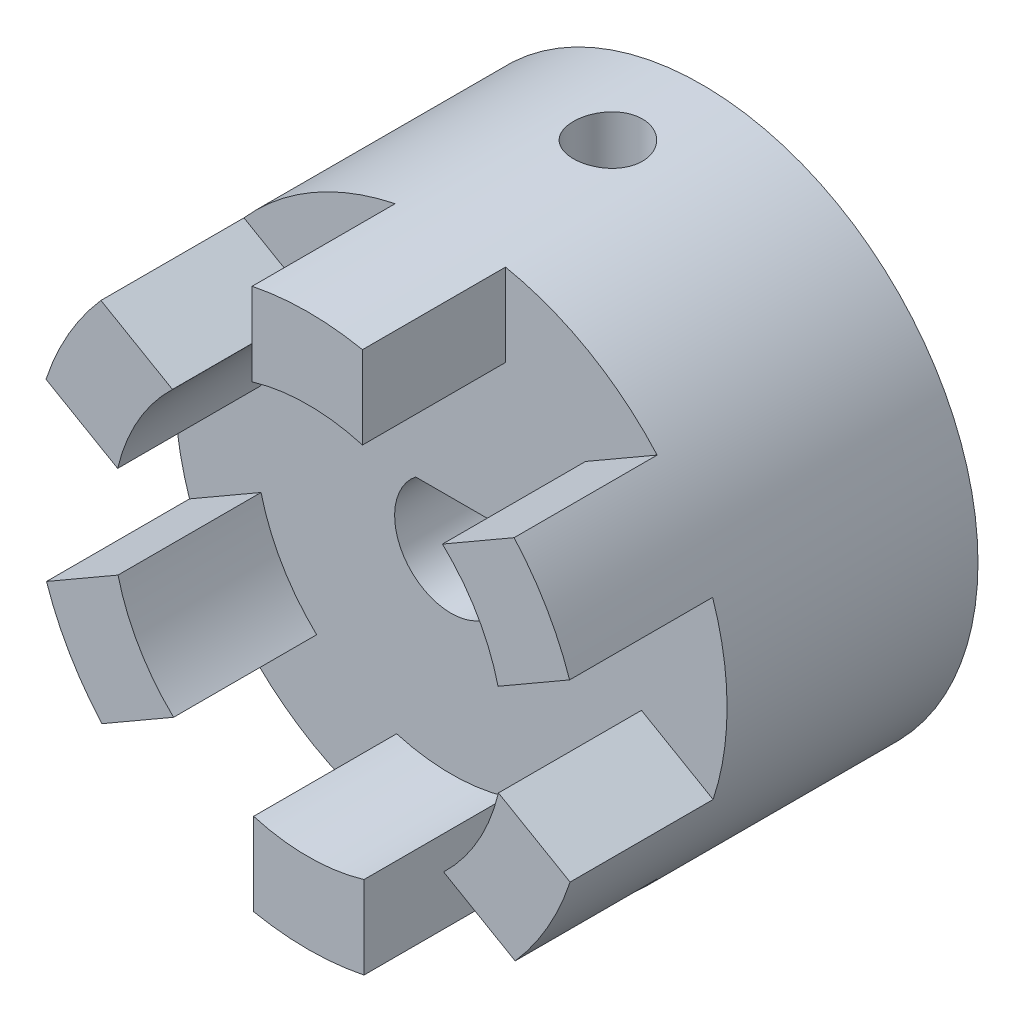
SolidWorks part; units mm, degrees
ref_plane "Front Plane" through (0, 0, 0) normal (0, 0, 1) x (1, 0, 0)
ref_plane "Top Plane" through (0, 0, 0) normal (0, 1, 0) x (1, 0, 0)
ref_plane "Right Plane" through (0, 0, 0) normal (1, 0, 0) x (0, 0, -1)
sketch "Sketch1" plane through (0, 0, 0) normal (0, 0, 1) x (1, 0, 0)
  line L0 (0, 0) -> (0, 27.2309) construction
  line L1 (21.0719, -6.3225) -> (21.0842, -6.3296) construction
  line L6 (4.3394, 14.9843) -> (4.3394, 21.5678)
  line L7 (16.0114, 15.0875) -> (16.0237, 15.0946) construction
  line L8 (15.1762, -3.6115) -> (20.8871, -6.9087)
  line L9 (-4.4605, 14.9487) -> (-4.4605, 21.5431)
  line L10 (5.0605, -21.4101) -> (5.0605, -21.4243) construction
  line L12 (-16.0114, -15.0875) -> (-16.0237, -15.0946) construction
  line L13 (-21.0719, 6.3225) -> (-21.0842, 6.3296) construction
  line L15 (-2.8284, 3.5) -> (2.8284, 3.5)
  line L17 (10.7157, 11.3372) -> (16.4266, 14.6344)
  line L18 (10.8071, -11.2502) -> (16.5085, -14.542)
  line L19 (-4.3394, -14.9843) -> (-4.3394, -21.5678)
  line L21 (-15.1762, 3.6115) -> (-20.8871, 6.9087)
  line L23 (15.1465, 3.7341) -> (20.848, 7.0258)
  line L25 (-10.7157, -11.3372) -> (-16.4266, -14.6344)
  line L26 (-15.1465, -3.7341) -> (-20.848, -7.0258)
  line L27 (-10.8071, 11.2502) -> (-16.5085, 14.542)
  line L31 (4.4605, -14.9487) -> (4.4605, -21.5431)
  line L41 (-5.0605, 21.4101) -> (-5.0605, 21.4243) construction
  circle A1 centre (0, 0) radius 15.6
  circle A2 centre (0, 0) radius 22
  arc A3 (-2.8284, 3.5) -> (2.8284, 3.5) centre (0, 0) ccw
  circle A4 centre (0, 0) radius 10
  point P2 (0, 0)
  point P7 (0, 0)
  point P8 (14.7356, 2.804)
  point P11 (0, 0)
  point P12 (21.0237, 6.4345)
  point P20 (14.759, -2.6778)
  point P25 (0, 0)
  point P27 (0, 0)
  point P33 (0, 0)
  point P35 (0, 3.5)
  point P36 (0, 4.5)
  point P37 (0, 0)
  point P65 (-4.4396, 21.5474)
  point P68 (4.345, 21.5667)
  point P71 (0, 0)
  point P72 (0, 0)
  point P73 (0, 0)
  point P74 (16.4308, 14.6297)
  point P77 (20.8524, 7.0127)
  point P80 (20.8848, -6.9155)
  point P83 (16.5044, -14.5466)
  point P86 (4.4583, -21.5435)
  point P89 (-4.3378, -21.5681)
  point P92 (-16.4265, -14.6345)
  point P95 (-20.8474, -7.0276)
  point P98 (-20.8881, 6.9056)
  point P101 (-16.5085, 14.542)
  dimension "D4" = 44
  dimension "D5" = 9
  dimension "D6" = 20
  dimension "D7" = 1
extrude "Boss-Extrude1" add sketch "Sketch1" along normal blind 11.4 contours L6 A2 L9 A1 | L23 A2 L17 A1 | L18 A2 L8 A1 | L19 A2 L31 A1 | L26 A2 L25 A1 | L27 A2 L21 A1 region at (-0.0617, 18.62, 0) region at (16.0946, 9.3635, 0) region at (-16.1563, 9.2566, 0) region at (16.1563, -9.2566, 0) region at (-16.0946, -9.3635, 0) region at (0.0617, -18.62, 0)
extrude "Boss-Extrude2" add sketch "Sketch1<6>" against normal blind 20 contours L17 A2 L6 A1 | L6 A2 L9 A1 | L9 A2 L27 A1 | L27 A2 L21 A1 | L21 A2 L26 A1 | L26 A2 L25 A1 | L25 A2 L19 A1 | L19 A2 L31 A1 | L31 A2 L18 A1 | L18 A2 L8 A1 | L8 A2 L23 A1 | L23 A2 L17 A1 | A1 A4 | A4 A3 L15 region at (-0.0617, 18.62, 0) region at (9.378, 16.3659, 0) region at (7.5262, 13.1584, 0) region at (16.0946, 9.3635, 0) region at (-9.4843, 16.3045, 0) region at (18.8623, 0.0614, 0) region at (-16.1563, 9.2566, 0) region at (-18.8623, -0.0614, 0) region at (16.1563, -9.2566, 0) region at (-16.0946, -9.3635, 0) region at (9.4843, -16.3045, 0) region at (-9.378, -16.3659, 0) region at (0.0617, -18.62, 0) region at (-9.7172, 0, 0)
sketch "Sketch1<6>" plane through (0, 0, 0) normal (0, 0, 1) x (1, 0, 0) same geometry as "Sketch1"
sketch "Sketch2" plane through (0, 0, 0) normal (0, 1, 0) x (1, 0, 0)
  line L0 (0, 0) -> (0, 7.5) construction
  line L1 (0, 7.5) -> (0, 17.5) construction
  circle A0 centre (0, 12.5) radius 2.75
  point P3 (0, 12.5)
  dimension "D3" = 5.5
  dimension "D1" = 7.5
  dimension "D2" = 10
extrude "Cut-Extrude1" cut sketch "Sketch2" along normal blind 30
